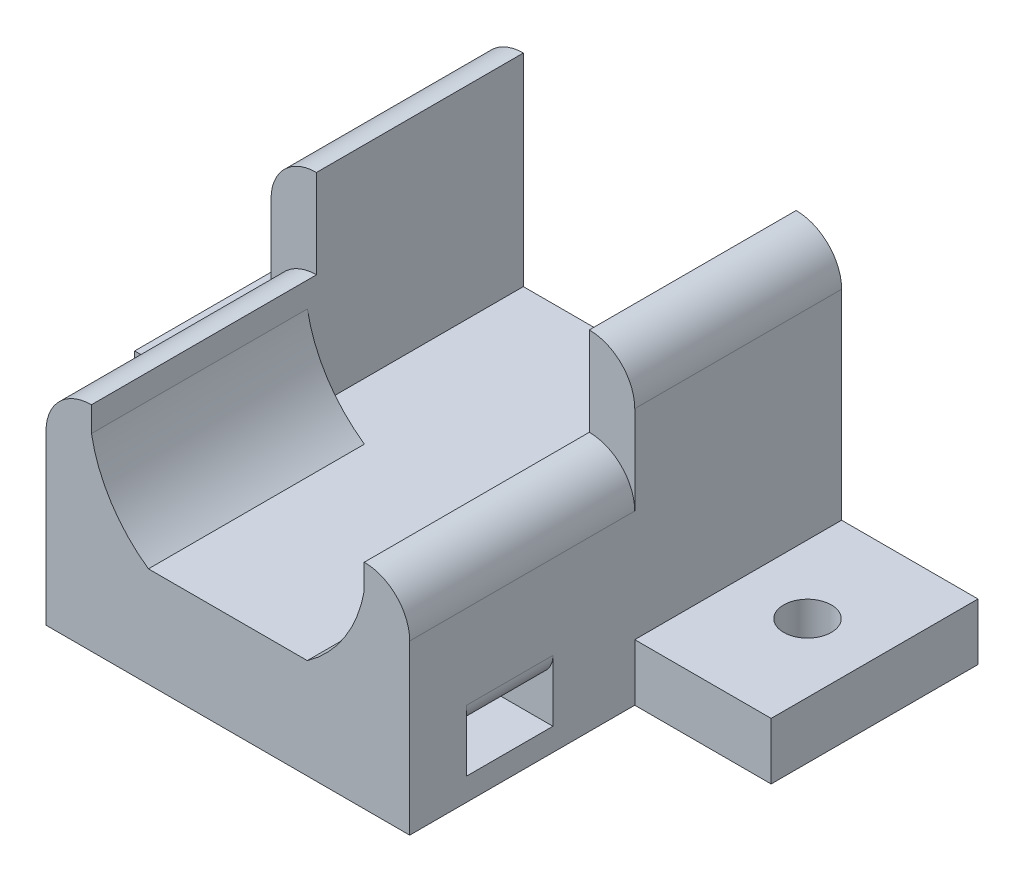
SolidWorks part; units mm, degrees
ref_plane "Front Plane" through (0, 0, 0) normal (0, 0, 1) x (1, 0, 0)
ref_plane "Top Plane" through (0, 0, 0) normal (0, 1, 0) x (1, 0, 0)
ref_plane "Right Plane" through (0, 0, 0) normal (1, 0, 0) x (0, 0, -1)
sketch "Sketch2" plane through (0, 0, 0) normal (0, 1, 0) x (1, 0, 0)
  line L1 (-8, -9.5) -> (8, -9.5)
  line L2 (-8, -9.5) -> (-8, 9.5)
  line L3 (-8, 9.5) -> (8, 9.5)
  line L4 (8, -9.5) -> (8, 9.5)
  line L5 (-8, -9.5) -> (8, 9.5) construction
  line L6 (-8, 9.5) -> (8, -9.5) construction
  point P0 (0, 0)
  dimension "D1" = 16
  dimension "D2" = 19
extrude "Boss-Extrude1" add sketch "Sketch2" along normal blind 13.3
sketch "Sketch3" plane through (0, 13.3, 0) normal (0, 1, 0) x (1, 0, 0)
  line L0 (8, 9.5) -> (-8, 9.5) construction
  line L1 (-6, -9.5) -> (6, -9.5)
  line L2 (-6, -9.5) -> (-6, 9.5)
  line L3 (-6, 9.5) -> (6, 9.5)
  line L4 (6, -9.5) -> (6, 9.5)
  line L5 (-6, -9.5) -> (6, 9.5) construction
  line L6 (-6, 9.5) -> (6, -9.5) construction
  point P0 (0, 0)
  dimension "D1" = 12
extrude "Cut-Extrude1" cut sketch "Sketch3" against normal blind 8.9
fillet "Fillet1" radius 2 2 edges at (-8, 13.3, 0) (8, 13.3, 0)
sketch "Sketch4" plane through (0, 0, 0) normal (1, 0, 0) x (0, 0, -1)
  line L0 (8.8, 0) -> (-8.8, 0) construction
  line L1 (-9.5, 13.3) -> (0.4, 13.3)
  line L2 (-9.5, 13.3) -> (-9.5, 9.4)
  line L3 (-9.5, 9.4) -> (0.4, 9.4)
  line L4 (0.4, 13.3) -> (0.4, 9.4)
  dimension "D1" = 9.9
  dimension "D2" = 9.4
extrude "Cut-Extrude2" cut sketch "Sketch4" against normal through all both and the other way through all
fillet "Fillet2" radius 2 2 edges at (-8, 9.4, 4.55) (8, 9.4, 4.55)
sketch "Sketch5" plane through (0, 0, 0) normal (1, 0, 0) x (0, 0, -1)
  line L0 (8.8, 0) -> (-8.8, 0) construction
  line L1 (-7, 2.7) -> (-3.2, 2.7)
  line L2 (-7, 2.7) -> (-7, 1)
  line L3 (-7, 1) -> (-3.2, 1)
  line L4 (-3.2, 2.7) -> (-3.2, 1)
  line L5 (-9.5, 7.4) -> (-9.5, 0) construction
  dimension "D1" = 3.8
  dimension "D2" = 1.7
  dimension "D3" = 1
  dimension "D4" = 2.5
extrude "Cut-Extrude3" cut sketch "Sketch5" against normal through all both and the other way through all
sketch "Sketch6" plane through (0, 0, 0) normal (0, 1, 0) x (1, 0, 0)
  line L0 (6, 9.5) -> (-6, 9.5) construction
  line L1 (-14, 9.5) -> (14, 9.5)
  line L2 (0, 9.5) -> (0, 0.4)
  line L3 (-14, 0.4) -> (14, 0.4)
  line L4 (14, 9.5) -> (14, 0.4)
  line L6 (0, -7.315) -> (0, 7.315) construction
  line L7 (-14, 9.5) -> (-14, 0.4)
  dimension "D1" = 9.1
  dimension "D2" = 14
extrude "Boss-Extrude2" add sketch "Sketch6" along normal blind 2.5 contours L4 L1 L2 L3 | L1 L7 L3 L2 region at (-7, 0, -4.95) region at (7, 0, -4.95)
sketch "Sketch7" plane through (0, 2.5, 0) normal (0, 1, 0) x (1, 0, 0)
  line L0 (-8, 9.5) -> (-8, 0.4) construction
  line L1 (-14, 9.5) -> (-8, 9.5) construction
  line L2 (0, -7.315) -> (0, 7.315) construction
  circle A0 centre (-11, 5) radius 1.05
  circle A1 centre (11, 5) radius 1.05
  dimension "D1" = 2.1
  dimension "D2" = 3
  dimension "D3" = 4.5
extrude "Cut-Extrude4" cut sketch "Sketch7" against normal through all both and the other way through all
fillet "Fillet3" radius 1 2 edges at (-8, 2.7, 5.1) (8, 2.7, 5.1)
sketch "Sketch14" plane through (0, 0, 0) normal (0, 0, 1) x (1, 0, 0)
  line L1 (-6, 13.3) -> (6, 13.3)
  line L2 (-6, 13.3) -> (-6, 4.4)
  line L3 (-6, 4.4) -> (6, 4.4)
  line L4 (6, 13.3) -> (6, 4.4)
sketch "Sketch15" plane through (0, 0, 0) normal (0, 0, 1) x (1, 0, 0)
  line L0 (0, -7.315) -> (0, 7.315) construction
  line L1 (-6, 4.4) -> (6, 4.4) construction
  line L2 (-6, 4.4) -> (6, 4.4)
  line L7 (-6, 13.3) -> (6, 13.3)
  line L8 (-6, 13.3) -> (-6, 9.4)
  line L9 (-6, 9.4) -> (6, 9.4)
  line L10 (6, 13.3) -> (6, 9.4)
  line L11 (6, 13.3) -> (6, 4.4)
  line L12 (6, 13.3) -> (6, 4.4)
  line L13 (-6, 13.3) -> (-6, 4.4)
  circle A0 centre (0, 9.4) radius 6.1
  dimension "D1" = 12.2
  dimension "D2" = 5
extrude "Boss-Extrude3" add sketch "Sketch14" along normal blind 9.5
extrude "Cut-Extrude9" cut sketch "Sketch15" against normal through all both and the other way through all contours L7 A0 | L9 A0 L7 | L9 A0 L2 | A0 L7 L8 | L10 L9 L8 L7 region at (0, 7.0861, 0) region at (0, 11.2761, 0) region at (-5.6057, 12.492, 0) region at (0, 14.1952, 0)
